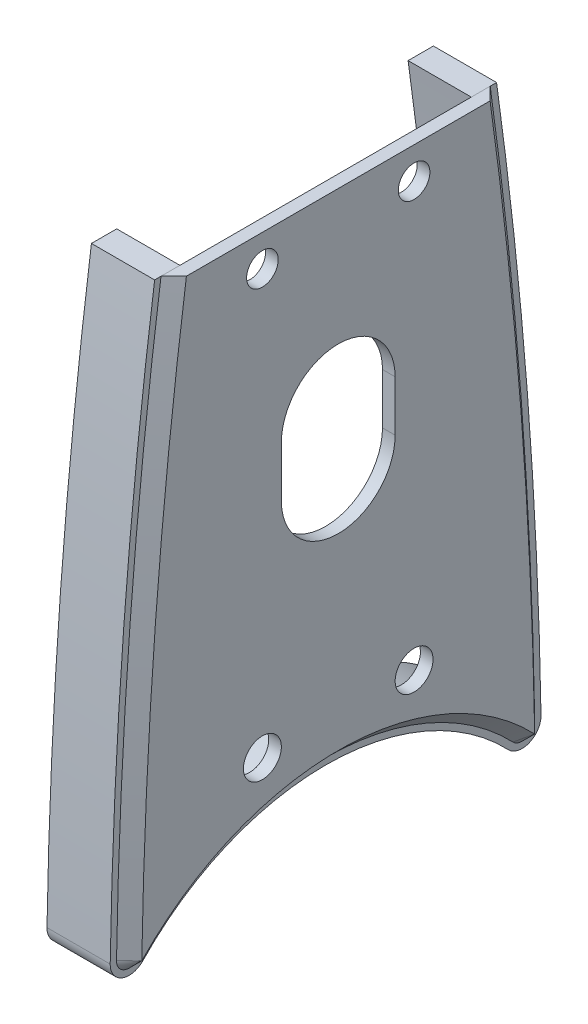
SolidWorks part; units mm, degrees
ref_plane "Front Plane" through (0, 0, 0) normal (0, 0, 1) x (1, 0, 0)
ref_plane "Top Plane" through (0, 0, 0) normal (0, 1, 0) x (1, 0, 0)
ref_plane "Right Plane" through (0, 0, 0) normal (1, 0, 0) x (0, 0, -1)
sketch "Sketch1" plane through (0, 0, 0) normal (1, 0, 0) x (0, 0, -1)
  line L0 (0, 160) -> (0, 115) construction
  line L1 (-12, 115) -> (12, 115) construction
  line L2 (-27.0529, 120) -> (27.0529, 120)
  arc A0 (-33.9907, -0.7948) -> (33.9907, -0.7948) centre (0, 0) ccw construction
  arc A1 (-19.6111, 163.925) -> (19.6111, 163.925) centre (0, 160) cw construction
  arc A2 (-33.9907, -0.7948) -> (-19.6111, 163.925) centre (715.8043, 16.7375) cw construction
  arc A3 (33.9907, -0.7948) -> (19.6111, 163.925) centre (-715.8043, 16.7375) ccw construction
  arc A4 (-33.9907, -0.7948) -> (-27.0529, 120) centre (715.8043, 16.7375) cw construction
  arc A5 (33.9907, -0.7948) -> (27.0529, 120) centre (-715.8043, 16.7375) ccw construction
  circle A6 centre (-12, 115) radius 2.5
  circle A7 centre (12, 115) radius 2.5
  arc A8 (-34.0825, 29.7649) -> (-27.0529, 120) centre (715.8043, 16.7375) cw
  arc A9 (34.0825, 29.7649) -> (27.0529, 120) centre (-715.8043, 16.7375) ccw
  arc A10 (-28.9144, 27.6398) -> (28.9144, 27.6398) centre (0, 0) cw
  arc A11 (28.9144, 27.6398) -> (34.0825, 29.7649) centre (31.083, 29.7128) ccw
  arc A12 (-28.9144, 27.6398) -> (-34.0825, 29.7649) centre (-31.083, 29.7128) cw
  point P20 (0, 115)
  point P26 (0, 0)
  dimension "D1" = 34
  dimension "D2" = 20
  dimension "D4" = 750
  dimension "D5" = 750
  dimension "D8" = 5
  dimension "D9" = 5
  dimension "D11" = 40
  dimension "D12" = 3
  dimension "D3" = 160
  dimension "D6" = 45
  dimension "D7" = 24
  dimension "D10" = 40
extrude "Boss-Extrude1" add sketch "Sketch1" along normal blind 2
sketch "Sketch2" plane through (0, 0, 0) normal (-1, 0, 0) x (0, 0, 1)
  line L0 (-15.5, 101.2) -> (15.5, 70.2) construction
  line L1 (0, 89.7) -> (0, 81.7) construction
  line L2 (9, 89.7) -> (9, 81.7)
  line L3 (-9, 89.7) -> (-9, 81.7)
  arc A0 (9, 89.7) -> (-9, 89.7) centre (0, 89.7) ccw
  arc A1 (-9, 81.7) -> (9, 81.7) centre (0, 81.7) ccw
  point P0 (0, 85.7)
  point P2 (0, 160)
  point P4 (0, 85.7)
  point P12 (0, 120)
  point P13 (0, 0)
  dimension "D1" = 74.3
  dimension "D2" = 8
  dimension "18" = 18
  dimension "D4" = 160
extrude "Cut-Extrude1" cut sketch "Sketch2" against normal blind 2
sketch "Sketch4" plane through (0, 0, 0) normal (-1, 0, 0) x (0, 0, 1)
  line L2 (-27.0529, 120) -> (-23.0529, 120)
  line L3 (27.0529, 120) -> (-27.0529, 120)
  line L4 (27.0529, 120) -> (23.0529, 120)
  line L5 (-23.0529, 120) -> (-27.0529, 120)
  line L7 (27.0529, 120) -> (23.0529, 120) construction
  arc A8 (-23.0529, 120) -> (-29.8756, 38.6445) centre (719.8043, 16.7375) ccw
  arc A9 (29.8756, 38.6445) -> (23.0529, 120) centre (-719.8043, 16.7375) ccw
  arc A10 (25.1614, 36.0958) -> (-25.1614, 36.0958) centre (0, 0) ccw
  arc A11 (-29.8756, 38.6445) -> (-25.1614, 36.0958) centre (-26.8769, 38.5569) ccw
  arc A12 (25.1614, 36.0958) -> (29.8756, 38.6445) centre (26.8769, 38.5569) ccw
  arc A13 (34.0825, 29.7649) -> (27.0529, 120) centre (-715.8043, 16.7375) ccw
  arc A14 (-27.0529, 120) -> (-34.0825, 29.7649) centre (715.8043, 16.7375) ccw
  arc A15 (-34.0825, 29.7649) -> (-28.9144, 27.6398) centre (-31.083, 29.7128) ccw
  arc A16 (28.9144, 27.6398) -> (-28.9144, 27.6398) centre (0, 0) ccw
  arc A17 (28.9144, 27.6398) -> (34.0825, 29.7649) centre (31.083, 29.7128) ccw
  arc A18 (34.0825, 29.7649) -> (27.0529, 120) centre (-715.8043, 16.7375) ccw
  arc A19 (-27.0529, 120) -> (-34.0825, 29.7649) centre (715.8043, 16.7375) ccw
  arc A20 (-34.0825, 29.7649) -> (-28.9144, 27.6398) centre (-31.083, 29.7128) ccw
  arc A21 (28.9144, 27.6398) -> (-28.9144, 27.6398) centre (0, 0) ccw
  arc A22 (28.9144, 27.6398) -> (34.0825, 29.7649) centre (31.083, 29.7128) ccw
  arc M6 (34.0825, 29.7649) -> (27.0529, 120) centre (-715.8043, 16.7375) ccw
  line M7 (27.0529, 120) -> (-27.0529, 120)
  arc M8 (-27.0529, 120) -> (-34.0825, 29.7649) centre (715.8043, 16.7375) ccw
  arc M9 (-34.0825, 29.7649) -> (-28.9144, 27.6398) centre (-31.083, 29.7128) ccw
  arc M10 (-28.9144, 27.6398) -> (28.9144, 27.6398) centre (0, 0) cw
  arc M11 (28.9144, 27.6398) -> (34.0825, 29.7649) centre (31.083, 29.7128) ccw
  dimension "D1" = 0
  dimension "D2" = 4
  dimension "D3" = 4
  dimension "D6" = 6
  dimension "D7" = 6
  dimension "D4" = 4
  dimension "4" = 4
extrude "Boss-Extrude3" add sketch "Sketch4" along normal blind 10 separate body contours A12 A10 A11 A8 A9 M7 M8 M9 M10 M11 M6 region at (0, 118.8446, -25.0529)
sketch "Sketch5" plane through (2, 0, 0) normal (1, 0, 0) x (0, 0, -1)
  line L0 (-12, 48) -> (12, 48) construction
  circle A0 centre (-12, 48) radius 3
  circle A1 centre (12, 48) radius 3
  dimension "D1" = 6
  dimension "D2" = 6
  dimension "D5" = 12
  dimension "D3" = 24
  dimension "D4" = 48
extrude "Cut-Extrude2" cut sketch "Sketch5" against normal blind 10
chamfer "Chamfer4" distance 3 angle 45 5 edges at (2, 74.9886, -31.9301) (2, 26.9382, -32.2239) (2, 40, 0) (2, 26.9382, 32.2239) (2, 74.9886, 31.9301)
